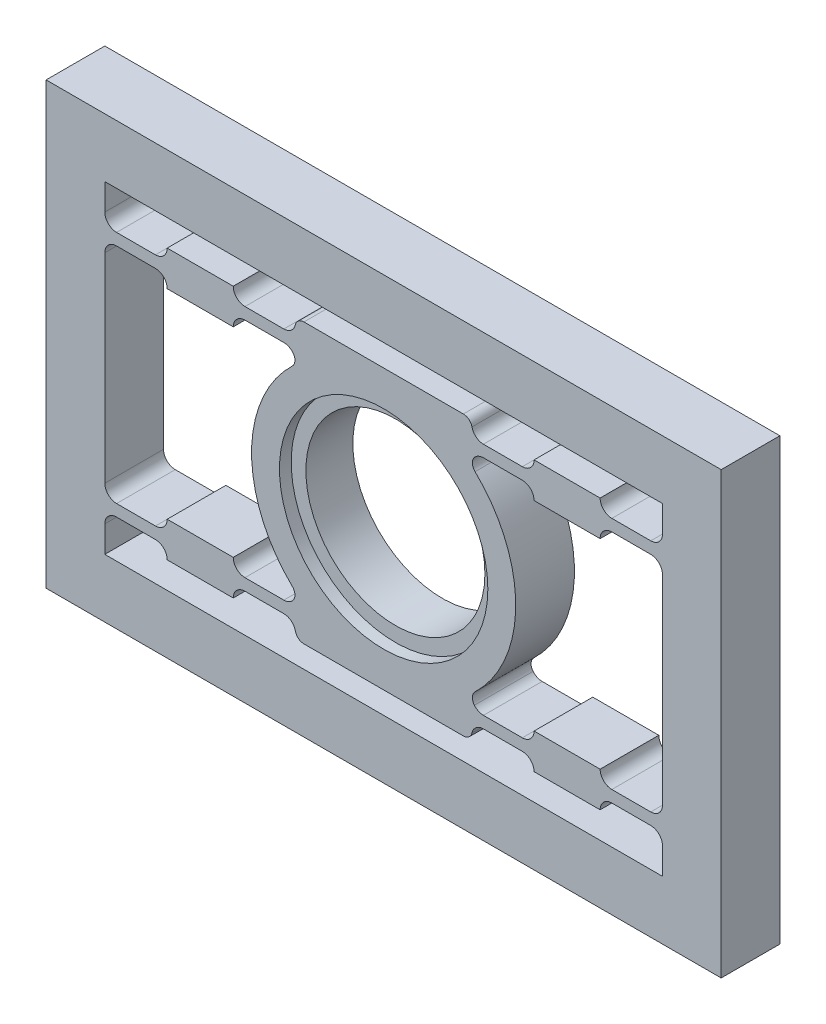
SolidWorks part; units mm, degrees
ref_plane "前视基准面" through (0, 0, 0) normal (0, 0, 1) x (1, 0, 0)
ref_plane "上视基准面" through (0, 0, 0) normal (0, 1, 0) x (1, 0, 0)
ref_plane "右视基准面" through (0, 0, 0) normal (1, 0, 0) x (0, 0, -1)
other "Configuration Table"
sketch "草图2" plane through (0, 0, 0) normal (0, 0, 1) x (1, 0, 0)
  circle A0 centre (0, 0) radius 7.1
  circle A1 centre (0, 0) radius 6.1
  circle A2 centre (0, 0) radius 9
  dimension "D1" = 14.2
  dimension "D2" = 12.2
  dimension "D3" = 18
extrude "凸台-拉伸1" add sketch "草图2" along normal blind 3.2 contours A0 A1 region at (-6.8992, 0, 0)
extrude "凸台-拉伸2" add sketch "草图2<3>" along normal blind 4 contours A2 A0 region at (-8.7454, 0, 0)
sketch "草图2<3>" plane through (0, 0, 0) normal (0, 0, 1) x (1, 0, 0) same geometry as "草图2"
sketch "草图3" plane through (0, 0, 0) normal (0, 0, 1) x (1, 0, 0)
  line L0 (6, 6.7082) -> (6, 9.5)
  line L1 (-6, -9.5) -> (6, -9.5)
  line L2 (-6, -9.5) -> (-6, -6.7082)
  line L3 (-6, 9.5) -> (6, 9.5)
  line L4 (6, -9.5) -> (6, -6.7082)
  line L5 (-6, -9.5) -> (-4.8059, -7.6094) construction
  line L6 (-6, 9.5) -> (-4.8059, 7.6094) construction
  line L7 (4.8059, 7.6094) -> (6, 9.5) construction
  line L8 (4.8059, -7.6094) -> (6, -9.5) construction
  line L9 (-6, 6.7082) -> (-6, 9.5)
  circle A0 centre (0, 0) radius 9 construction
  arc A1 (-6, -6.7082) -> (6, -6.7082) centre (0, 0) ccw
  arc A2 (6, 6.7082) -> (-6, 6.7082) centre (0, 0) ccw
  point P0 (0, 0)
  point P6 (6.3996, 14.0216)
  point P17 (-6.0466, 14.003)
  point P18 (5.9854, 11.2704)
  dimension "D1" = 12
  dimension "D2" = 9.5
extrude "凸台-拉伸3" add sketch "草图3" along normal up to surface (4 mm away) contours A2 L3 L9 | A2 L0 L3 | A1 L1 L4 | A1 L2 L1 region at (0, 9.1232, 0) region at (-5.8768, -8.1041, 0) up to face at (7.1, 0, 4)
sketch "草图4" plane through (0, 0, 0) normal (0, 0, 1) x (1, 0, 0)
  line L0 (-6, 9.5) -> (6, 9.5) construction
  line L1 (-19, -11) -> (19, -11)
  line L2 (-19, -11) -> (-19, 11)
  line L3 (-19, 11) -> (19, 11)
  line L4 (19, -11) -> (19, 11)
  line L5 (-19, -11) -> (19, 11) construction
  line L6 (-19, 11) -> (19, -11) construction
  line L7 (-23, -15) -> (23, -15)
  line L8 (-23, -15) -> (-23, 15)
  line L9 (-23, 15) -> (23, 15)
  line L10 (23, -15) -> (23, 15)
  line L11 (-23, -15) -> (23, 15) construction
  line L12 (-23, 15) -> (23, -15) construction
  point P0 (0, 0)
  point P6 (0, 0)
  dimension "D1" = 1.5
  dimension "D2" = 4
  dimension "D3" = 4
  dimension "D4" = 38
extrude "凸台-拉伸4" add sketch "草图4" along direction (0, 0, 1) on the side of the normal blind 4 separate body
sketch "草图5" plane through (0, 0, 0) normal (0, 0, 1) x (1, 0, 0)
  line L0 (0, 15) -> (0, -15) construction
  line L1 (23, 15) -> (-23, 15) construction
  line L2 (-23, -15) -> (23, -15) construction
  line L3 (-6, 8) -> (-19, 8) construction
  line L5 (-19, 11) -> (-19, -11) construction
  line L6 (6, 8) -> (19, 8) construction
  line L7 (-6, -8) -> (-19, -8) construction
  line L9 (6, -8) -> (19, -8) construction
  line L10 (-6, 6.7082) -> (-6, 9.5) construction
  line L11 (-19, 7.6) -> (-6, 7.6)
  line L12 (-19, 7.6) -> (-19, 8.4)
  line L13 (-19, 8.4) -> (-6, 8.4)
  line L14 (-6, 7.6) -> (-6, 8.4)
  line L15 (-19, 7.6) -> (-6, 8.4) construction
  line L16 (-19, 8.4) -> (-6, 7.6) construction
  line L17 (19, 7.6) -> (6, 8.4) construction
  line L18 (19, 8.4) -> (6, 7.6) construction
  line L19 (19, 7.6) -> (19, 8.4)
  line L20 (19, 7.6) -> (6, 7.6)
  line L21 (6, 7.6) -> (6, 8.4)
  line L22 (19, 8.4) -> (6, 8.4)
  line L23 (-6, -9.5) -> (-6, -6.7082) construction
  line L24 (-19, -8.4) -> (-6, -8.4)
  line L25 (-19, -8.4) -> (-19, -7.6)
  line L26 (-19, -7.6) -> (-6, -7.6)
  line L27 (-6, -8.4) -> (-6, -7.6)
  line L28 (-19, -8.4) -> (-6, -7.6) construction
  line L29 (-19, -7.6) -> (-6, -8.4) construction
  line L30 (19, -8.4) -> (6, -7.6) construction
  line L31 (19, -7.6) -> (6, -8.4) construction
  line L32 (19, -8.4) -> (19, -7.6)
  line L33 (19, -8.4) -> (6, -8.4)
  line L34 (6, -8.4) -> (6, -7.6)
  line L35 (19, -7.6) -> (6, -7.6)
  line L39 (0, 0) -> (-19, 0) construction
  line L40 (14.75, 6.8) -> (14.75, 9.2)
  line L41 (-14.75, 6.8) -> (-10.25, 6.8)
  line L42 (-14.75, 6.8) -> (-14.75, 9.2)
  line L43 (-14.75, 9.2) -> (-10.25, 9.2)
  line L44 (-10.25, 6.8) -> (-10.25, 9.2)
  line L45 (-14.75, 6.8) -> (-10.25, 9.2) construction
  line L46 (-14.75, 9.2) -> (-10.25, 6.8) construction
  line L47 (14.75, 6.8) -> (10.25, 9.2) construction
  line L48 (14.75, 9.2) -> (10.25, 6.8) construction
  line L49 (14.75, 6.8) -> (10.25, 6.8)
  line L50 (10.25, 6.8) -> (10.25, 9.2)
  line L51 (14.75, 9.2) -> (10.25, 9.2)
  line L52 (14.75, -9.2) -> (14.75, -6.8)
  line L53 (-14.75, -9.2) -> (-10.25, -9.2)
  line L54 (-14.75, -9.2) -> (-14.75, -6.8)
  line L55 (-14.75, -6.8) -> (-10.25, -6.8)
  line L56 (-10.25, -9.2) -> (-10.25, -6.8)
  line L57 (-14.75, -9.2) -> (-10.25, -6.8) construction
  line L58 (-14.75, -6.8) -> (-10.25, -9.2) construction
  line L59 (14.75, -9.2) -> (10.25, -6.8) construction
  line L60 (14.75, -6.8) -> (10.25, -9.2) construction
  line L61 (14.75, -9.2) -> (10.25, -9.2)
  line L62 (10.25, -9.2) -> (10.25, -6.8)
  line L63 (14.75, -6.8) -> (10.25, -6.8)
  point P8 (-12.5, 8)
  point P25 (12.5, 8)
  point P28 (-12.5, -8)
  point P37 (12.5, -8)
  point P42 (-12.5, 8)
  point P52 (12.5, 8)
  point P53 (-12.5, -8)
  point P62 (12.5, -8)
  point P63 (-18.9072, 5.0782)
  point P64 (-18.2102, 6.6771)
  dimension "D1" = 0.8
  dimension "D2" = 16
  dimension "D3" = 0.8
  dimension "D4" = 4.5
extrude "凸台-拉伸5" add sketch "草图5" along normal up to surface (4 mm away) contours L11 L14 L13 L12 | L41 L44 L43 L42 | L49 L50 L51 L40 | L20 L21 L22 L19 | L33 L34 L35 L32 | L61 L62 L63 L52 | L53 L56 L55 L54 | L24 L27 L26 L25 up to face at (7.1, 0, 4)
fillet "圆角1" radius 0.8 32 edges at (19, 7.6, 2) (19, -7.6, 2) (-19, -7.6, 2) (-19, 7.6, 2) (-6, 7.6, 2) (6, 7.6, 2) (6, -7.6, 2) (-6, -7.6, 2) (-6, -8.4, 2) (6, -8.4, 2) (6, 8.4, 2) (-6, 8.4, 2) (-19, 8.4, 2) (19, 8.4, 2) (-19, -8.4, 2) (19, -8.4, 2) (-10.25, 7.6, 2) (-10.25, 8.4, 2) (-14.75, 8.4, 2) (-14.75, 7.6, 2) (14.75, 7.6, 2) (14.75, 8.4, 2) (10.25, 8.4, 2) (10.25, 7.6, 2) (14.75, -8.4, 2) (14.75, -7.6, 2) (10.25, -7.6, 2) (10.25, -8.4, 2) (-10.25, -8.4, 2) (-10.25, -7.6, 2) (-14.75, -7.6, 2) (-14.75, -8.4, 2)
fillet "圆角2" radius 0.6 8 edges at (-6, -9.5, 2) (6, 9.5, 2) (6, -9.5, 2) (-6, 9.5, 2) (6, -6.7082, 2) (-6, 6.7082, 2) (6, 6.7082, 2) (-6, -6.7082, 2)
